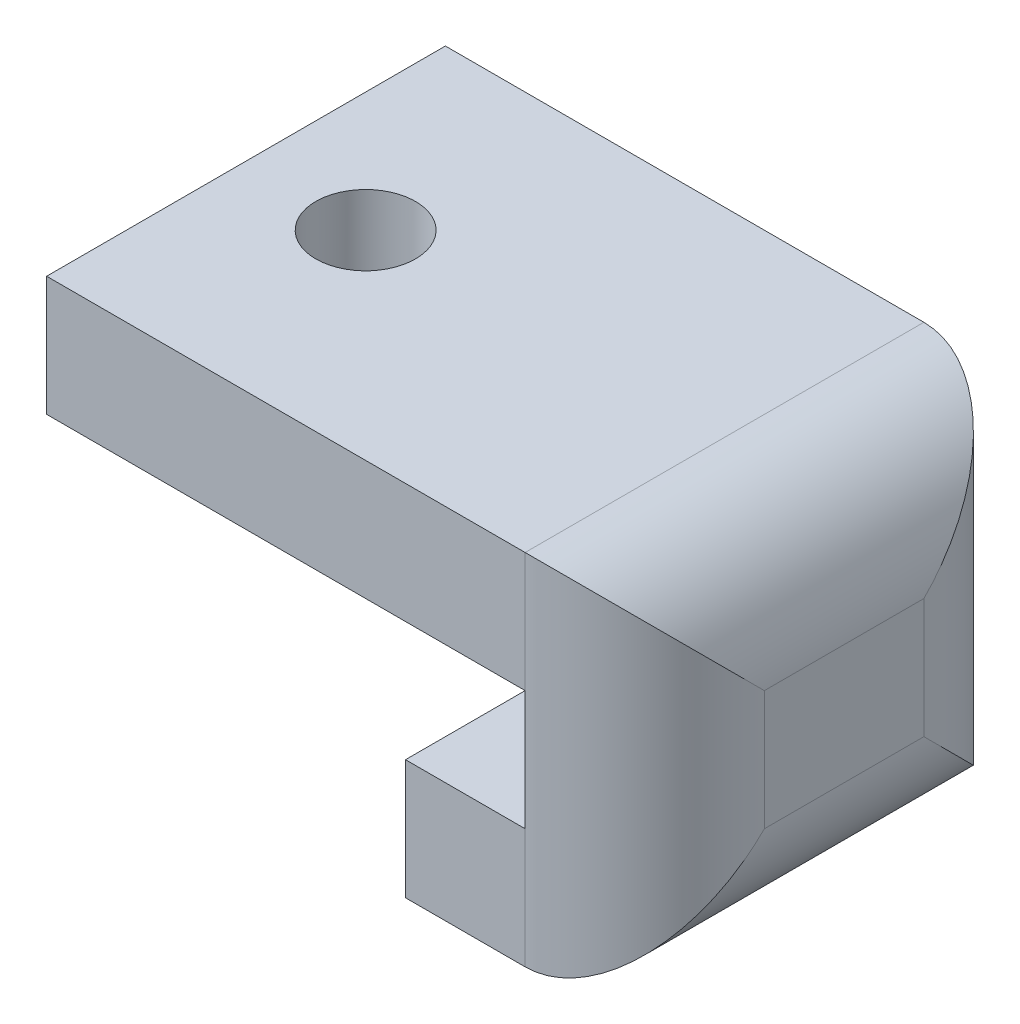
SolidWorks part; units mm, degrees
material "ABS generico"
ref_plane "Piano frontale" through (0, 0, 0) normal (0, 0, 1) x (1, 0, 0)
ref_plane "Piano superiore" through (0, 0, 0) normal (0, 1, 0) x (1, 0, 0)
ref_plane "Piano destro" through (0, 0, 0) normal (1, 0, 0) x (0, 0, -1)
sketch "Schizzo1" plane through (0, 0, 0) normal (0, 0, 1) x (1, 0, 0)
  line L0 (-6, 0) -> (6, 0)
  line L1 (6, 0) -> (6, -3)
  line L2 (6, -3) -> (3, -3)
  line L3 (3, -3) -> (3, -6)
  line L4 (3, -6) -> (9, -6)
  line L5 (9, -6) -> (9, 3)
  line L6 (9, 3) -> (-6, 3)
  line L7 (-6, 3) -> (-6, 0)
  dimension "D1" = 15
  dimension "D3" = 3
  dimension "D4" = 3
  dimension "D5" = 3
  dimension "D7" = 6
extrude "Estrusione-Estrusione1" add sketch "Schizzo1" along normal blind 10
fillet "Raccordo1" radius 3 4 edges at (9, -6, 5) (9, -1.5, 10) (9, 3, 5) (9, -1.5, 0)
hole_wizard "Foro filettato M3x0.5-1" positions "Schizzo3" profile "Schizzo2" tap size "M3x0.5" standard "Ansi Metric" end condition through all
sketch "Schizzo3" plane through (0, 3, 0) normal (0, 1, 0) x (1, 0, 0)
  line L0 (-3, -5) -> (-6, -5) construction
  line L1 (-6, -10) -> (-6, 0) construction
  line L3 (-3, -5) -> (-3, 0) construction
  line L4 (6, 0) -> (-6, 0) construction
  line L6 (-3, -5) -> (-3, -10) construction
  line L7 (6, -10) -> (-6, -10) construction
  point P0 (-3, -5)
  dimension "D1" = 3
sketch "Schizzo2" plane through (-3, 3, 5) normal (1, 0, 0) x (0, 0, 1)
  line L0 (0, 0) -> (0, 9)
  line L1 (0, 9) -> (1.25, 9)
  line L2 (1.25, 9) -> (1.25, 0)
  line L5 (1.25, 0) -> (0, 0)
  line L11 (0, -6.35) -> (0, 107.95) construction
  dimension "Thru Tap Drill Dia." = 2.5
  dimension "Thru Tap Drill Depth" = 9
cosmetic thread "Filettatura del foro1" parameters "D2"=3
